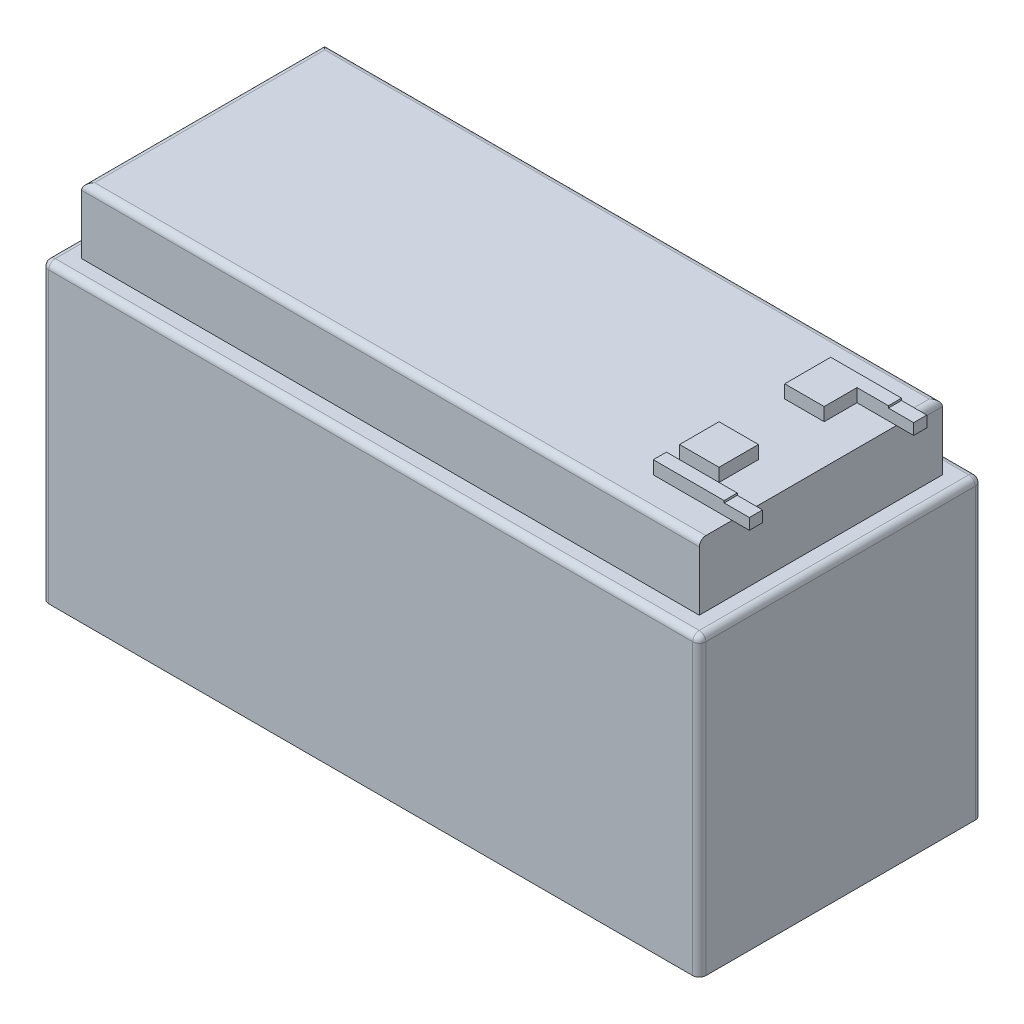
SolidWorks part; units mm, degrees
ref_plane "Ön Düzlem" through (0, 0, 0) normal (0, 0, 1) x (1, 0, 0)
ref_plane "Üst Düzlem" through (0, 0, 0) normal (0, 1, 0) x (1, 0, 0)
ref_plane "Sağ Düzlem" through (0, 0, 0) normal (1, 0, 0) x (0, 0, -1)
sketch "Sketch1" plane through (0, 0, 0) normal (0, 1, 0) x (1, 0, 0)
  line L1 (-50, -21.5) -> (50, -21.5)
  line L2 (-50, -21.5) -> (-50, 21.5)
  line L3 (-50, 21.5) -> (50, 21.5)
  line L4 (50, -21.5) -> (50, 21.5)
  line L5 (-50, -21.5) -> (50, 21.5) construction
  line L6 (-50, 21.5) -> (50, -21.5) construction
  circle A0 centre (0, 0) radius 3.4491 construction
  point P0 (0, 0)
  dimension "D3" = 6.8983
  dimension "D1" = 100
  dimension "D2" = 43
extrude "Boss-Extrude1" add sketch "Sketch1" along normal blind 55
sketch "Sketch2" plane through (0, 55, 0) normal (0, 1, 0) x (1, 0, 0)
  line L1 (-50, -21.5) -> (50, -21.5)
  line L2 (-50, -21.5) -> (-50, 21.5)
  line L3 (-50, 21.5) -> (50, 21.5)
  line L4 (50, -21.5) -> (50, 21.5)
  line L5 (50, 21.5) -> (-50, 21.5)
  line L6 (-50, 21.5) -> (-50, -21.5)
  line L7 (-50, -21.5) -> (50, -21.5)
  line L8 (50, -21.5) -> (50, 21.5)
  line L9 (50, 21.5) -> (-50, 21.5)
  line L10 (-50, 21.5) -> (-50, -21.5)
  line L11 (-50, -21.5) -> (50, -21.5)
  line L12 (50, -21.5) -> (50, 21.5)
  line L13 (-50, -21.5) -> (50, 21.5) construction
  line L14 (-50, 21.5) -> (50, -21.5) construction
  line L15 (-47, -18.5) -> (47, -18.5)
  line L16 (-47, -18.5) -> (-47, 18.5)
  line L17 (-47, 18.5) -> (47, 18.5)
  line L18 (47, -18.5) -> (47, 18.5)
  line L19 (-47, -18.5) -> (47, 18.5) construction
  line L20 (-47, 18.5) -> (47, -18.5) construction
  line L21 (35, 6.5) -> (41, 6.5)
  line L22 (35, 6.5) -> (35, 12.5)
  line L23 (35, 12.5) -> (41, 12.5)
  line L24 (41, 6.5) -> (41, 12.5)
  line L25 (35, 6.5) -> (41, 12.5) construction
  line L26 (35, 12.5) -> (41, 6.5) construction
  line L27 (35, -9.5) -> (41, -9.5)
  line L28 (35, -9.5) -> (35, -3.5)
  line L29 (35, -3.5) -> (41, -3.5)
  line L30 (41, -9.5) -> (41, -3.5)
  line L31 (35, -9.5) -> (41, -3.5) construction
  line L32 (35, -3.5) -> (41, -9.5) construction
  point P2 (0, 0)
  point P5 (0, 0)
  point P11 (38, 9.5)
  point P16 (38, -6.5)
  point P21 (38, 6.5)
  point P22 (38, -3.5)
  line M18 (50, -21.5) -> (50, 21.5)
  line M19 (50, 21.5) -> (-50, 21.5)
  line M20 (-50, 21.5) -> (-50, -21.5)
  line M21 (-50, -21.5) -> (50, -21.5)
  dimension "D2" = 3
  dimension "D3" = 3
  dimension "D4" = 6
  dimension "D5" = 6
  dimension "D6" = 6
  dimension "D7" = 6
  dimension "D8" = 10
  dimension "D9" = 6
  dimension "D10" = 6
  dimension "D1" = 0
extrude "Cut-Extrude1" cut sketch "Sketch2" against normal blind 10 contours L18 L15 L16 L17 M21 M18 M19 M20 | L21 L24 L23 L22 | L29 L30 L27 L28
sketch "Sketch3" plane through (0, 45, 0) normal (0, 1, 0) x (1, 0, 0)
  line L1 (41, -3.5) -> (35, -3.5)
  line L2 (41, -3.5) -> (41, -9.5)
  line L3 (41, -9.5) -> (35, -9.5)
  line L4 (35, -3.5) -> (35, -9.5)
extrude "Boss-Extrude2" add sketch "Sketch3" along normal blind 12
sketch "Sketch4" plane through (0, 45, 0) normal (0, 1, 0) x (1, 0, 0)
  line L1 (41, 12.5) -> (35, 12.5)
  line L2 (41, 12.5) -> (41, 6.5)
  line L3 (41, 6.5) -> (35, 6.5)
  line L4 (35, 12.5) -> (35, 6.5)
sketch "Sketch7" plane through (0, 0, 0) normal (0, -1, 0) x (1, 0, 0)
  circle A0 centre (0, 0) radius 2
  dimension "D1" = 4
extrude "Cut-Extrude2" cut sketch "Sketch7" against normal blind 10
extrude "Boss-Extrude3" add sketch "Sketch4" along normal blind 12
ref_plane "Plane1" through (0, 0, -12.5) normal (0, 0, 1) x (1, 0, 0)
sketch "Sketch5" plane through (0, 0, -12.5) normal (0, 0, 1) x (1, 0, 0)
  line L0 (35, 55) -> (35, 57)
  line L1 (35, 57) -> (45.779, 57)
  line L2 (45.779, 57) -> (45.779, 56.6894)
  line L3 (45.779, 56.6894) -> (49.6169, 56.6894)
  line L4 (49.6169, 56.6894) -> (49.6169, 55)
  line L5 (-47, 55) -> (47, 55) construction
  line L6 (49.6169, 55) -> (35, 55)
  dimension "D1" = 2
  dimension "D2" = 1.6894
extrude "Boss-Extrude4" add sketch "Sketch5" along normal mid plane 2
mirror "Mirror1" about plane through (0, 0, 0) normal (0, 0, 1) of "Boss-Extrude4"
fillet "Fillet1" radius 1 13 edges at (-50, 22.5, 21.5) (50, 22.5, 21.5) (50, 22.5, -21.5) (-50, 22.5, -21.5) (0, 45, -21.5) (-50, 45, 0) (0, 45, 21.5) (50, 45, 0) (47, 55, 16) (47, 55, -16) (0, 55, 18.5) (-47, 55, 0) (0, 55, -18.5)
